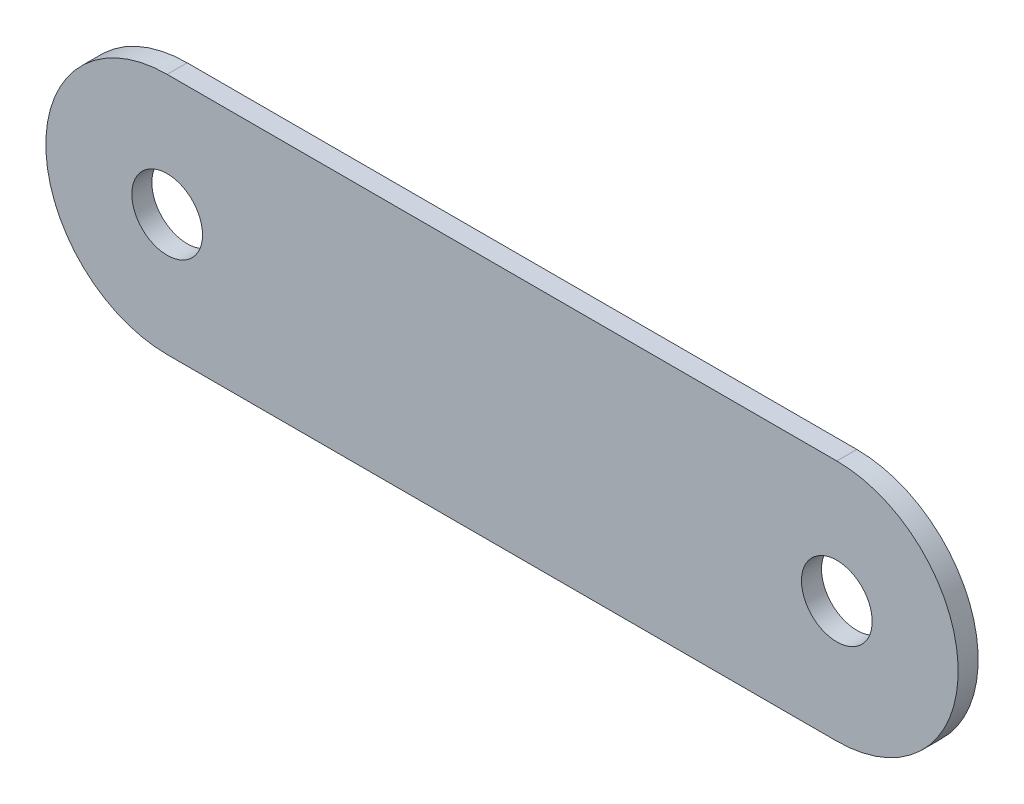
SolidWorks part; units mm, degrees
ref_plane "Front" through (0, 0, 0) normal (0, 0, 1) x (1, 0, 0)
ref_plane "Top" through (0, 0, 0) normal (0, 1, 0) x (1, 0, 0)
ref_plane "Right" through (0, 0, 0) normal (1, 0, 0) x (0, 0, -1)
sketch "Sketch1" plane through (0, 0, 0) normal (0, 0, 1) x (1, 0, 0)
  line L0 (-50.205, 0) -> (50.205, 0) construction
  line L1 (-50.205, 18.193) -> (50.205, 18.193)
  line L2 (-50.205, -18.193) -> (50.205, -18.193)
  arc A0 (-50.205, 18.193) -> (-50.205, -18.193) centre (-50.205, 0) ccw
  arc A1 (50.205, -18.193) -> (50.205, 18.193) centre (50.205, 0) ccw
  circle A2 centre (-50.205, 0) radius 5.3
  circle A4 centre (50.205, 0) radius 5.3
  point P2 (50.205, 0)
  point P3 (0, 0)
  dimension "D1" = 10.6
  dimension "D2" = 18.193
  dimension "D4" = 10.6
  dimension "D3" = 100.41
extrude "Boss-Extrude1" add sketch "Sketch1" along normal blind 3
